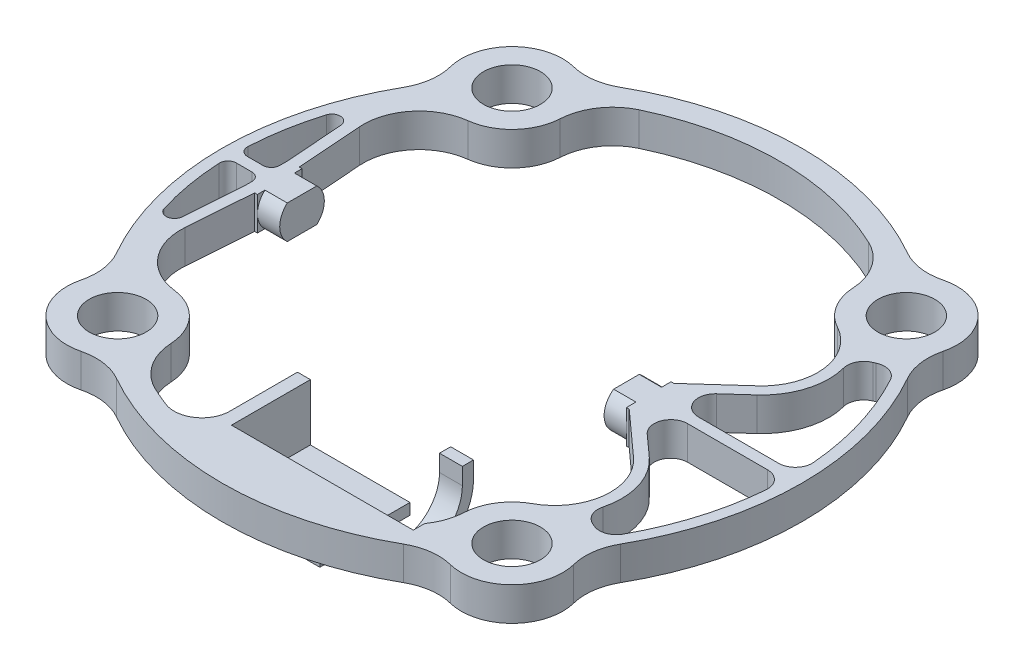
SolidWorks part; units mm, degrees
other "Markup1"
sketch "Sketch20" plane through (52, 6, -52) normal (0.9882, 0.0434, -0.1465) x (-0.1478, 0.0276, -0.9886)
ref_plane "Front Plane" through (0, 0, 0) normal (0, 0, 1) x (1, 0, 0)
ref_plane "Top Plane" through (0, 0, 0) normal (0, 1, 0) x (1, 0, 0)
ref_plane "Right Plane" through (0, 0, 0) normal (1, 0, 0) x (0, 0, -1)
sketch "Sketch1" plane through (0, 0, 0) normal (0, 1, 0) x (1, 0, 0)
  line L1 (-35.3553, -35.3553) -> (35.3553, -35.3553) construction
  line L2 (-35.3553, -35.3553) -> (-35.3553, 35.3553) construction
  line L3 (-35.3553, 35.3553) -> (35.3553, 35.3553) construction
  line L4 (35.3553, -35.3553) -> (35.3553, 35.3553) construction
  line L5 (-35.3553, -35.3553) -> (35.3553, 35.3553) construction
  line L6 (-35.3553, 35.3553) -> (35.3553, -35.3553) construction
  circle A0 centre (0, 0) radius 52
  circle A1 centre (0, 0) radius 48
  circle A2 centre (0, 0) radius 50 construction
  circle A3 centre (35.3553, 35.3553) radius 5.1
  circle A4 centre (-35.3553, 35.3553) radius 5.1
  circle A5 centre (-35.3553, -35.3553) radius 5.1
  circle A6 centre (35.3553, -35.3553) radius 5.1
  circle A7 centre (35.3553, 35.3553) radius 9.1
  circle A8 centre (-35.3553, 35.3553) radius 9.1
  circle A9 centre (-35.3553, -35.3553) radius 9.1
  circle A10 centre (35.3553, -35.3553) radius 9.1
  dimension "D1" = 96
  dimension "D2" = 104
  dimension "D3" = 100
  dimension "D4" = 10.2
  dimension "D5" = 10.2
  dimension "D6" = 10.2
  dimension "D7" = 10.2
  dimension "D8" = 4
extrude "Boss-Extrude1" add sketch "Sketch1" along normal blind 6 contours A8 A1 A7 A0 | A1 A8 A0 A4 | A0 A8 A4 | A0 A8 A1 A4 | A1 A8 A4 | A9 A1 A8 A0 | A1 A9 A5 | A1 A9 A0 A5 | A0 A9 A5 | A0 A9 A1 A5 | A10 A1 A9 A0 | A1 A10 A6 | A0 A10 A1 A6 | A0 A10 A6 | A1 A10 A0 A6 | A10 A0 A7 A1 | A0 A7 A3 | A0 A7 A1 A3 | A1 A7 A0 A3 | A1 A7 A3 region at (49.0102, 0, 15.4585) region at (39.943, 0, -30.075) region at (39.073, 0, -39.073) region at (39.073, 0, 39.073) region at (39.943, 0, 30.075) region at (31.3721, 0, -31.3721) region at (31.3721, 0, 31.3721) region at (30.075, 0, -39.943) region at (0, 0, -48.6096) region at (30.075, 0, 39.943) region at (0, 0, 51.3904) region at (-31.3721, 0, -31.3721) region at (-30.075, 0, -39.943) region at (-39.073, 0, -39.073) region at (-39.073, 0, 39.073) region at (-30.075, 0, 39.943) region at (-31.3721, 0, 31.3721) region at (-41.5843, 0, -27.9071) region at (-39.943, 0, -30.075) region at (-39.943, 0, 30.075)
fillet "Fillet1" radius 10 16 edges at (-27.2586, 3, 39.5091) (-39.5091, 3, 27.2586) (39.5091, 3, 27.2586) (27.2586, 3, 39.5091) (-39.5091, 3, -27.2586) (-27.2586, 3, -39.5091) (27.2586, 3, -39.5091) (39.5091, 3, -27.2586) (-42.5896, 3, 29.8349) (-29.8349, 3, 42.5896) (29.8349, 3, 42.5896) (42.5896, 3, 29.8349) (42.5896, 3, -29.8349) (29.8349, 3, -42.5896) (-29.8349, 3, -42.5896) (-42.5896, 3, -29.8349)
sketch "Sketch2" plane through (0, 6, 0) normal (0, 1, 0) x (1, 0, 0)
  line L0 (-41.15, 11.9734) -> (-41.15, -15.376) construction
  line L1 (24.02, 8.956) -> (24.02, -12.6154) construction
  line L2 (-47.833, 4) -> (47.833, 4) construction
  line L3 (-47.833, -4) -> (47.833, -4) construction
  line L4 (-47.833, 4) -> (-37.65, 4)
  line L5 (-37.65, 4) -> (-37.65, -4)
  line L6 (-37.65, -4) -> (-47.833, -4)
  line L7 (47.833, 4) -> (20.52, 4)
  line L8 (20.52, 4) -> (20.52, -4)
  line L9 (20.52, -4) -> (47.833, -4)
  arc A0 (-43.3702, 20.5675) -> (-43.3702, -20.5675) centre (0, 0) ccw construction
  arc A1 (43.3702, -20.5675) -> (43.3702, 20.5675) centre (0, 0) ccw construction
  arc A2 (-47.833, 4) -> (-47.833, -4) centre (0, 0) ccw
  arc A3 (47.833, 4) -> (47.833, -4) centre (0, 0) cw
  arc M11 (-43.3702, -20.5675) -> (-43.3702, 20.5675) centre (0, 0) cw
  arc M19 (43.3702, 20.5675) -> (43.3702, -20.5675) centre (0, 0) cw
  dimension "D1" = 41.15
  dimension "D2" = 24.02
  dimension "D3" = 4
  dimension "D4" = 4
  dimension "D5" = 3.5
  dimension "D6" = 3.5
extrude "Boss-Extrude2" add sketch "Sketch2" against normal up to surface (6 mm away) contours L6 L5 L4 M11 | L8 L9 L7 M19 region at (-42.7973, 6, 0) region at (34.2322, 6, 0) up to face at (0, 0, 0)
sketch "Sketch3" plane through (0, 6, 0) normal (0, 1, 0) x (1, 0, 0)
  line L0 (-42.15, 4) -> (-42.15, -4)
  line L2 (-47.833, 4) -> (-37.65, 4) construction
  line L3 (-37.65, -4) -> (-47.833, -4) construction
  line L4 (25.02, 4) -> (25.02, -4)
  line L5 (47.833, 4) -> (20.52, 4) construction
  line L6 (20.52, -4) -> (47.833, -4) construction
  line L7 (-37.65, 4) -> (-37.65, -4) construction
  line L8 (20.52, 4) -> (20.52, -4) construction
  line L9 (-42.15, 4) -> (-43.3702, 20.5675)
  line L10 (-42.15, -4) -> (-43.3702, -20.5675)
  line L11 (25.02, 4) -> (43.3702, 20.5675)
  line L12 (25.02, -4) -> (43.3702, -20.5675)
  arc A0 (-43.3702, 20.5675) -> (-43.3702, -20.5675) centre (0, 0) ccw
  arc A1 (43.3702, 20.5675) -> (43.3702, -20.5675) centre (0, 0) cw
  arc A2 (43.3702, -20.5675) -> (47.833, -4) centre (0, 0) ccw construction
  arc M7 (-43.3702, -20.5675) -> (-47.833, -4) centre (0, 0) cw
  line M8 (-47.833, -4) -> (-37.65, -4)
  line M10 (-37.65, 4) -> (-47.833, 4)
  arc M11 (-47.833, 4) -> (-43.3702, 20.5675) centre (0, 0) cw
  arc M19 (43.3702, 20.5675) -> (47.833, 4) centre (0, 0) cw
  line M20 (47.833, 4) -> (20.52, 4)
  line M22 (20.52, -4) -> (47.833, -4)
  arc M23 (47.833, -4) -> (43.3702, -20.5675) centre (0, 0) cw
  dimension "D1" = 4.5
  dimension "D2" = 4.5
extrude "Boss-Extrude3" add sketch "Sketch3" along direction (0, 1, 0) on the side against the normal up to surface (6 mm away) contours L9 M10 M11 | L10 M8 M7 | L11 M20 M19 | L12 M22 M23 region at (-44.6805, 6, -9.9724) region at (-44.6805, 6, 9.9724) region at (39.0615, 6, -9.6497) region at (39.0615, 6, 9.6497) up to face at (-1.4275, 0, 0)
sketch "Sketch4" plane through (0, 6, 0) normal (0, 1, 0) x (1, 0, 0)
  line L0 (-45.0759, 16.4974) -> (-44.3027, 6)
  line L1 (-44.3027, 6) -> (-47.6235, 6)
  line L2 (-47.6235, -6) -> (-44.3027, -6)
  line L3 (-44.3027, -6) -> (-45.0759, -16.4974)
  line L4 (-42.15, -4) -> (-43.3702, -20.5675) construction
  line L5 (-42.15, 4) -> (-43.3702, 20.5675) construction
  line L6 (-42.15, 4) -> (-37.65, 4) construction
  line L7 (-37.65, -4) -> (-42.15, -4) construction
  line L8 (44.2293, 18.6486) -> (30.2197, 6)
  line L9 (30.2197, 6) -> (47.6235, 6)
  line L10 (44.2293, -18.6486) -> (30.2197, -6)
  line L11 (30.2197, -6) -> (47.6235, -6)
  line L12 (25.02, 4) -> (20.52, 4) construction
  line L13 (25.02, 4) -> (43.3702, 20.5675) construction
  line L14 (25.02, -4) -> (43.3702, -20.5675) construction
  line L15 (20.52, -4) -> (25.02, -4) construction
  circle A0 centre (0, 0) radius 48
  dimension "D5" = 96
  dimension "D1" = 2
  dimension "D2" = 2
  dimension "D3" = 2
  dimension "D4" = 2
  dimension "D6" = 2
  dimension "D7" = 2
  dimension "D8" = 2
  dimension "D9" = 2
fillet "Fillet2" radius 10 4 edges at (43.3702, 3, 20.5675) (43.3702, 3, -20.5675) (-43.3702, 3, 20.5675) (-43.3702, 3, -20.5675)
sketch "Sketch5" plane through (0, 6, 0) normal (0, 1, 0) x (1, 0, 0)
  line L0 (32.939, 11.1497) -> (34.2793, 9.6652)
  line L1 (34.2793, 9.6652) -> (27.02, 3.1112)
  line L2 (32.939, -11.1497) -> (34.2793, -9.6652)
  line L3 (34.2793, -9.6652) -> (27.02, -3.1112)
  line L4 (27.02, -3.1112) -> (27.02, 3.1112)
  circle A0 centre (35.3553, 35.3553) radius 9.1
  circle A1 centre (35.3553, -35.3553) radius 9.1
  circle A2 centre (35.3553, -35.3553) radius 11.1
  circle A3 centre (35.3553, 35.3553) radius 11.1
  circle A4 centre (0, 0) radius 50
  circle A5 centre (26.2377, 18.5721) radius 12
  circle A6 centre (26.2377, -18.5721) radius 12
  arc A7 (45.1856, -25.7344) -> (45.1856, 25.7344) centre (0, 0) ccw construction
  arc A8 (32.939, 11.1497) -> (31.0113, 27.3591) centre (26.2377, 18.5721) ccw construction
  arc A9 (31.0113, -27.3591) -> (32.939, -11.1497) centre (26.2377, -18.5721) ccw construction
  dimension "D1" = 2
  dimension "D2" = 2
  dimension "D3" = 2
  dimension "D4" = 2
  dimension "D5" = 2
  dimension "D6" = 2
extrude "Cut-Extrude2" cut sketch "Sketch5" against normal blind 6 contours A6 A2 A4 A3 A5 L1 L4 L3 region at (40.5745, 6, 0)
sketch "Sketch6" plane through (0, 6, 0) normal (0, 1, 0) x (1, 0, 0)
  line L0 (27.02, 0.9819) -> (49.9904, 0.9819)
  line L1 (27.02, -3.1112) -> (27.02, 3.1112) construction
  line L2 (27.02, -1.0181) -> (49.9896, -1.0181)
  line L3 (27.02, 0.9819) -> (27.02, -1.0181)
  line L4 (49.9904, 0.9819) -> (51.1942, 0.9819)
  line L5 (51.1942, 0.9819) -> (51.1942, -1.0181)
  line L6 (51.1942, -1.0181) -> (49.9896, -1.0181)
  arc A0 (42.2845, -26.6837) -> (42.2845, 26.6837) centre (0, 0) ccw construction
  dimension "D1" = 2
extrude "Boss-Extrude4" add sketch "Sketch6" against normal up to surface (6 mm away) up to face at (-35.3553, 0, -30.2553)
fillet "Fillet3" radius 3 8 edges at (27.02, 3, -0.9819) (27.02, 3, 1.0181) (36.7582, 3, 24.3443) (42.2845, 3, 26.6837) (49.9896, 3, 1.0181) (49.9904, 3, -0.9819) (36.7582, 3, -24.3443) (42.2845, 3, -26.6837)
fillet "Fillet4" radius 3 2 edges at (27.02, 3, -3.1112) (27.02, 3, 3.1112)
sketch "Sketch7" plane through (0, 0, 0) normal (0, -1, 0) x (1, 0, 0)
  line L0 (-45.4032, 20.9416) -> (-44.15, 3.9264)
  line L1 (-44.15, 3.9264) -> (-44.15, -3.9264)
  line L2 (-44.15, -3.9264) -> (-45.4032, -20.9416)
  line L3 (-43.0089, -15.6622) -> (-42.15, -4) construction
  line L4 (-43.0089, 15.6622) -> (-42.15, 4) construction
  line L5 (-44.15, 1) -> (-51.4245, 1)
  line L6 (-51.4245, 1) -> (-51.4245, -1)
  line L7 (-51.4245, -1) -> (-44.15, -1)
  circle A0 centre (0, 0) radius 50
  arc A1 (-45.1856, 25.7344) -> (-45.1856, -25.7344) centre (0, 0) ccw construction
  point P14 (-42.5795, 9.8311)
  dimension "D1" = 2
  dimension "D2" = 2
  dimension "D3" = 2
  dimension "D4" = 2
  dimension "D5" = 1
  dimension "D6" = 1
extrude "Cut-Extrude3" cut sketch "Sketch7" against normal blind 6 contours L0 A0 L5 L1 | L7 A0 L2 L1 region at (-46.776, 0, 8.3346) region at (-46.776, 0, -8.3346)
fillet "Fillet5" radius 1.5 8 edges at (-44.15, 3, -3.9264) (-44.15, 3, 3.9264) (-44.15, 3, 1) (-44.15, 3, -1) (-49.99, 3, 1) (-49.99, 3, -1) (-45.4032, 3, -20.9416) (-45.4032, 3, 20.9416)
sketch "Sketch8" plane through (-37.65, 0, 0) normal (1, 0, 0) x (0, 0, -1)
  line L0 (-25.7344, 0) -> (25.7344, 0) construction
  line L2 (-6.5981, 8.7795) -> (6.5981, 8.7795)
  line L3 (-6.5981, 8.7795) -> (-6.5981, -2.7795)
  line L4 (-6.5981, -2.7795) -> (6.5981, -2.7795)
  line L5 (6.5981, 8.7795) -> (6.5981, -2.7795)
  line L6 (-6.5981, 8.7795) -> (6.5981, -2.7795) construction
  line L7 (-6.5981, -2.7795) -> (6.5981, 8.7795) construction
  circle A0 centre (0, 3) radius 4
  dimension "D2" = 8
  dimension "D1" = 3
extrude "Cut-Extrude4" cut sketch "Sketch8" against normal blind 4
sketch "Sketch9" plane through (20.52, 0, 0) normal (-1, 0, 0) x (0, 0, 1)
  line L1 (-6.0027, 9.9205) -> (6.0027, 9.9205)
  line L2 (-6.0027, 9.9205) -> (-6.0027, -4.4662)
  line L3 (-6.0027, -4.4662) -> (6.0027, -4.4662)
  line L4 (6.0027, 9.9205) -> (6.0027, -4.4662)
  line L5 (-6.0027, 9.9205) -> (6.0027, -4.4662) construction
  line L6 (-6.0027, -4.4662) -> (6.0027, 9.9205) construction
  circle A0 centre (0, 2.7271) radius 4
  dimension "D1" = 8
extrude "Cut-Extrude5" cut sketch "Sketch9" against normal blind 4
sketch "Sketch10" plane through (0, 6, 0) normal (0, 1, 0) x (1, 0, 0)
  line L0 (-20.1589, -28) -> (21.0577, -28) construction
  line L1 (-20.1589, -42.15) -> (16.3069, -42.15) construction
  line L2 (-8.15, -28) -> (-8.15, -45.3576) construction
  line L3 (-10.4647, -28) -> (-10.4647, -46.8454)
  line L4 (-8.15, -42.15) -> (14.7, -42.15)
  line L5 (-8.15, -42.15) -> (-8.15, -28)
  line L6 (-8.15, -28) -> (14.7, -28)
  line L7 (14.7, -42.15) -> (14.7, -28)
  line L8 (14.7, -42.15) -> (18.95, -42.15)
  line L9 (14.7, -42.15) -> (14.7, -28)
  line L10 (14.7, -28) -> (18.95, -28)
  line L11 (18.95, -42.15) -> (18.95, -28)
  line L12 (-10.4647, -28) -> (-8.15, -28)
  line L13 (-8.15, -28) -> (-8.15, -42.15)
  line L14 (-8.15, -42.15) -> (18.95, -42.15)
  line L15 (18.95, -42.15) -> (18.95, -44.101)
  arc A0 (-20.5675, -43.3702) -> (20.5675, -43.3702) centre (0, 0) ccw construction
  arc A1 (-10.4647, -46.8454) -> (18.95, -44.101) centre (0, 0) ccw
  dimension "D1" = 28
  dimension "D2" = 14.15
  dimension "D3" = 8.15
  dimension "D4" = 22.85
  dimension "D5" = 4.25
extrude "Boss-Extrude5" add sketch "Sketch10" along direction (0, 1, 0) on the side against the normal up to surface (6 mm away) contours L3 A1 L15 L8 L4 L5 L12 region at (0.632, 6, 42.9201) up to face at (-46.1845, 0, -5.5419)
sketch "Sketch11" plane through (0, 0, 0) normal (0, -1, 0) x (1, 0, 0)
  line L0 (-8.15, 28) -> (-8.15, 42.15) construction
  line L1 (-10.4647, 28) -> (-8.15, 28)
  line L2 (-10.4647, 28) -> (-10.4647, 42.15)
  line L3 (-10.4647, 42.15) -> (-8.15, 42.15)
  line L4 (-8.15, 28) -> (-8.15, 42.15)
  line L5 (-10.4647, 42.15) -> (9.7, 42.15)
  line L6 (-10.4647, 42.15) -> (-10.4647, 44.15)
  line L7 (-10.4647, 44.15) -> (9.7, 44.15)
  line L8 (9.7, 42.15) -> (9.7, 44.15)
  dimension "D1" = 2
  dimension "D2" = 17.85
extrude "Boss-Extrude6" add sketch "Sketch11" along normal blind 6.15 contours L5 L8 L7 L6 L3 | L1 L4 L3 L2 region at (-9.3073, 0, 35.075) region at (-0.3823, 0, 43.15)
sketch "Sketch12" plane through (18.95, 0, 0) normal (1, 0, 0) x (0, 0, -1)
  line L0 (-42.15, -6.15) -> (-42.15, 0) construction
  line L1 (-44.15, 3) -> (-25.85, 3)
  circle A0 centre (-35, 3) radius 7.15
  circle A1 centre (-35, 3) radius 9.15
  line M2 (-44.101, 0) -> (-42.15, 0)
  line M3 (-42.15, 0) -> (-42.15, 6)
  dimension "D2" = 14.3
  dimension "D3" = 2
  dimension "D1" = 7.15
extrude "Boss-Extrude7" add sketch "Sketch12" against normal blind 4.1 contours A1 L1 A0 M2 M3 region at (18.95, 2.7999, 26.85)
sketch "Sketch13" plane through (0, 6, 0) normal (0, 1, 0) x (1, 0, 0)
  line L0 (18.95, -42.15) -> (24.1394, -42.15)
  line L1 (24.1394, -42.15) -> (18.95, -46.449)
  line L2 (18.95, -46.449) -> (18.95, -42.15)
extrude "Boss-Extrude8" add sketch "Sketch13" against normal blind 6
sketch "Sketch14" plane through (0, 3, 0) normal (0, 1, 0) x (1, 0, 0)
  line L1 (14.85, -25.85) -> (18.95, -25.85)
  line L2 (14.85, -25.85) -> (14.85, -27.85)
  line L3 (14.85, -27.85) -> (18.95, -27.85)
  line L4 (18.95, -25.85) -> (18.95, -27.85)
extrude "Boss-Extrude9" add sketch "Sketch14" along normal blind 3
sketch "Sketch15" plane through (-8.15, 0, 0) normal (1, 0, 0) x (0, 0, -1)
  line L0 (-28, -6.15) -> (-28, 6) construction
  line L1 (-42.15, -6.15) -> (-28, -6.15)
  line L2 (-42.15, -6.15) -> (-42.15, -4.15)
  line L3 (-42.15, -4.15) -> (-28, -4.15)
  line L4 (-28, -6.15) -> (-28, -4.15)
  dimension "D1" = 2
extrude "Boss-Extrude10" add sketch "Sketch15" along normal blind 17.85
sketch "Sketch16" plane through (0, -6.15, 0) normal (0, -1, 0) x (-1, 0, 0)
  line L0 (10.4647, -28) -> (-9.7, -28) construction
  line L1 (-9.7, -42.15) -> (-4.7, -42.15)
  line L2 (-9.7, -42.15) -> (-9.7, -28)
  line L3 (-9.7, -28) -> (-4.7, -28)
  line L4 (-4.7, -42.15) -> (-4.7, -28)
  dimension "D1" = 5
extrude "Boss-Extrude11" add sketch "Sketch16" along normal blind 2.25
sketch "Sketch17" plane through (9.7, 0, 0) normal (1, 0, 0) x (0, 0, -1)
  line L0 (-28, -4.15) -> (-42.15, -4.15) construction
  circle A0 centre (-35.4211, -6.275) radius 1.5
  dimension "D2" = 3
  dimension "D1" = 2.125
extrude "Cut-Extrude6" cut sketch "Sketch17" against normal blind 3.5
sketch "Sketch18" plane through (9.7, 0, 0) normal (1, 0, 0) x (0, 0, -1)
  line L0 (-42.15, -6.15) -> (-28, -6.15)
  line L2 (-42.15, -6.15) -> (-28, -6.15)
  line L3 (-42.15, -6.15) -> (-42.15, -8.4)
  line L4 (-42.15, -8.4) -> (-28, -8.4)
  line L5 (-28, -6.15) -> (-28, -8.4)
  circle A0 centre (-35.4211, -6.275) radius 2.125
  line M5 (-42.15, -6.15) -> (-42.15, -8.4)
  line M6 (-42.15, -8.4) -> (-28, -8.4)
  line M7 (-28, -8.4) -> (-28, -4.15)
extrude "Cut-Extrude7" cut sketch "Sketch18" against normal blind 5.5 contours A0 L0 M5 M6 | A0 L4 L2 M7 region at (9.7, -7.3306, 39.6105) region at (9.7, -7.3239, 30.8829)
fillet "Fillet6" radius 5 2 edges at (7.2, -6.15, 37.5424) (7.2, -6.15, 33.2998)
fillet "Fillet7" radius 5 1 edges at (-0.3823, 0, 44.15)
fillet "Fillet8" radius 5 1 edges at (-10.4647, 3, 46.8454)
sketch "Sketch19" plane through (0, 6, 0) normal (0, 1, 0) x (1, 0, 0)
  line L0 (-8.15, -42.15) -> (22.5214, -42.15) construction
  line L1 (18.95, -25.85) -> (24.45, -25.85)
  line L2 (18.95, -25.85) -> (18.95, -42.15)
  line L3 (18.95, -42.15) -> (24.45, -42.15)
  line L4 (24.45, -25.85) -> (24.45, -42.15)
  dimension "D1" = 0
  dimension "D2" = 5.5
extrude "Cut-Extrude8" cut sketch "Sketch19" against normal blind 13.5
fillet "Fillet9" radius 5 1 edges at (16.9, 0, 43.6442)
